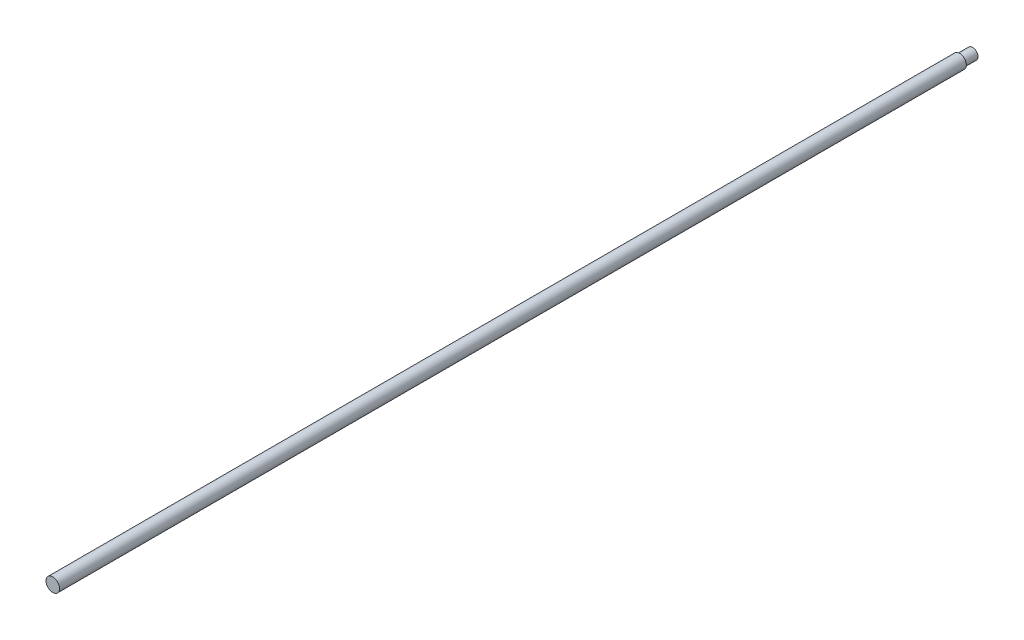
SolidWorks part; units mm, degrees
ref_plane "Plan de face" through (0, 0, 0) normal (0, 0, 1) x (1, 0, 0)
ref_plane "Plan de dessus" through (0, 0, 0) normal (0, 1, 0) x (1, 0, 0)
ref_plane "Plan de droite" through (0, 0, 0) normal (1, 0, 0) x (0, 0, -1)
sketch "Esquisse1" plane through (0, 0, 0) normal (0, 0, 1) x (1, 0, 0)
  circle A0 centre (0, 0) radius 2.5
  dimension "D1" = 5
extrude "Boss.-Extru.1" add sketch "Esquisse1" along normal blind 340
sketch "Esquisse2" plane through (0, 0, 0) normal (0, 0, -1) x (-1, 0, 0)
  circle A0 centre (0, 0) radius 2
  dimension "D1" = 4
extrude "Enlèv. mat.-Extru.1" cut sketch "Esquisse2" against normal blind 4.8 flip side to cut
hole_wizard "Trou taraudé M2.5x0.451" positions "Esquisse3" profile "Esquisse4" tap size "M2.5x0.45" standard "Ansi Metric"
sketch "Esquisse3" plane through (0, 0, 0) normal (0, 0, -1) x (-1, 0, 0)
  point P0 (0, 0)
sketch "Esquisse4" plane through (0, 0, 0) normal (1, 0, 0) x (0, 1, 0)
  line L0 (0, 0) -> (0, 7.8659)
  line L1 (0, 7.8659) -> (1.025, 7.25)
  line L2 (1.025, 7.25) -> (1.025, 0)
  line L5 (1.025, 0) -> (0, 0)
  line L10 (0, 7.8659) -> (-1.025, 7.25) construction
  line L11 (0, -6.35) -> (0, 107.95) construction
  dimension "Diamètre du trou pour taraudage" = 2.05
  dimension "Profondeur du trou pour taraudage" = 7.25
  dimension "Angle de pointe" = 118
cosmetic thread "Filetage de perçage1" parameters "D1"=5, "D2"=2.5
